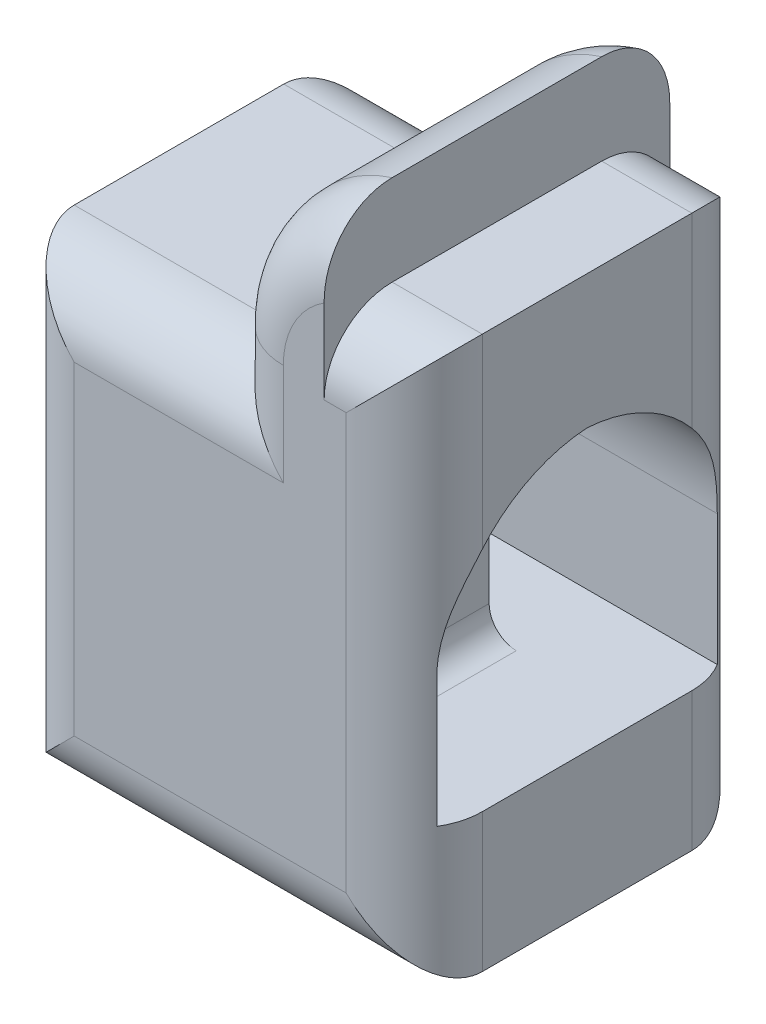
SolidWorks part; units mm, degrees
ref_plane "Front Plane" through (0, 0, 0) normal (0, 0, 1) x (1, 0, 0)
ref_plane "Top Plane" through (0, 0, 0) normal (0, 1, 0) x (1, 0, 0)
ref_plane "Right Plane" through (0, 0, 0) normal (1, 0, 0) x (0, 0, -1)
sketch "Sketch1" plane through (0, 0, 0) normal (0, 0, 1) x (1, 0, 0)
  line L0 (-139.1464, 0) -> (210.8536, 0) construction
  line L2 (-144.0044, -48.147) -> (166.7822, -48.147)
  line L3 (-144.0044, -48.147) -> (-144.0044, 51.853)
  line L4 (-144.0044, 51.853) -> (129.8735, 51.853)
  line L5 (226.7822, 11.853) -> (226.7822, 46.0483)
  line L6 (162.976, 133.7076) -> (166.7822, 133.7076)
  line L7 (129.8735, 103.7076) -> (129.8735, 51.853)
  line L9 (226.7822, 73.7076) -> (226.7822, 46.0483)
  line L12 (129.8735, 103.7076) -> (162.976, 103.7076)
  line L13 (162.976, 133.7076) -> (162.976, 103.7076)
  arc A0 (166.7822, 133.7076) -> (226.7822, 73.7076) centre (166.7822, 73.7076) cw
  arc A1 (166.7822, -48.147) -> (226.7822, 11.853) centre (166.7822, 11.853) ccw
  dimension "D2" = 60
  dimension "D1" = 350
  dimension "D3" = 30
  dimension "D4" = 100
sketch "Sketch2" plane through (0, 0, 0) normal (0, 0, 1) x (1, 0, 0)
  line L1 (-37.0212, -102.3945) -> (112.9173, -102.3945)
  line L2 (-37.0212, -102.3945) -> (-37.0212, 66.5681)
  line L3 (-37.0212, 66.5681) -> (39.8215, 66.5681)
  line L4 (112.9173, -102.3945) -> (112.9173, 63.3181)
  line L5 (129.8735, 103.7076) -> (162.976, 103.7076) construction
  line L7 (112.9173, 63.3181) -> (112.9173, 100.4576)
  line L12 (112.9173, 100.4576) -> (79.8148, 100.4576)
  line L13 (79.8148, 133.7076) -> (79.8148, 100.4576)
  line L14 (39.8215, 78.9736) -> (39.8215, 66.5681)
  arc A0 (39.8215, 78.9736) -> (79.8148, 133.7076) centre (97.272, 78.9736) cw
  dimension "D1" = 33.25
extrude "Boss-Extrude1" add sketch "Sketch2" along normal mid plane 127
sketch "Sketch3" plane through (112.9173, 0, 0) normal (1, 0, 0) x (0, 0, -1)
  line L5 (51.5, 51.5) -> (-51.5, 51.5)
  line L6 (51.5, 51.5) -> (51.5, -51.5)
  line L7 (51.5, -51.5) -> (-51.5, -51.5)
  line L8 (-51.5, 51.5) -> (-51.5, -51.5)
  line L9 (51.5, 51.5) -> (-51.5, -51.5) construction
  line L10 (51.5, -51.5) -> (-51.5, 51.5) construction
  point P0 (0, 0)
  dimension "D1" = 103
  dimension "D2" = 103
extrude "Cut-Extrude1" cut sketch "Sketch3" against normal through all
ref_plane "Plane1" through (37.9481, 0, 0) normal (-1, 0, 0) x (0, 0, 1)
sketch "Sketch5" plane through (37.9481, 0, 0) normal (-1, 0, 0) x (0, 0, 1)
  line L0 (51.5, -51.5) -> (-51.5, -51.5) construction
  line L1 (19, -51.5) -> (-19, -51.5)
  line L2 (19, -51.5) -> (19, -21.5)
  line L4 (-19, -51.5) -> (-19, -21.5)
  line L5 (0, -48.147) -> (0, 11.853) construction
  line L6 (-51.5, 51.5) -> (51.5, 51.5) construction
  arc A0 (19, -21.5) -> (-19, -21.5) centre (0, -21.5) ccw
  point P12 (-24.6088, -51.5)
  dimension "D1" = 38
  dimension "D2" = 73
extrude "Boss-Extrude2" add sketch "Sketch5" along normal mid plane 40
fillet "Fillet1" radius 55 2 edges at (37.9481, 51.5, 51.5) (37.9481, 51.5, -51.5)
sketch "Sketch6" plane through (17.9481, 0, 0) normal (-1, 0, 0) x (0, 0, 1)
  circle A0 centre (0, -21.5) radius 10
  dimension "D1" = 20
extrude "Cut-Extrude2" cut sketch "Sketch6" against normal through all
fillet "Fillet2" radius 10 2 edges at (57.9481, -51.5, 0) (17.9481, -51.5, 0)
sketch "Sketch7" plane through (112.9173, 0, 0) normal (1, 0, 0) x (0, 0, -1)
  line L1 (-12.8471, -33.7257) -> (12.1529, -33.7257)
  line L2 (-12.8471, -33.7257) -> (-12.8471, -8.7257)
  line L3 (-12.8471, -8.7257) -> (12.1529, -8.7257)
  line L4 (12.1529, -33.7257) -> (12.1529, -8.7257)
  line L6 (12.1529, -33.7257) -> (37.1529, -33.7257)
  line L7 (37.1529, -33.7257) -> (37.1529, -8.7257)
  line L8 (12.1529, -33.7257) -> (12.1529, -8.7257)
  line L9 (12.1529, -8.7257) -> (37.1529, -8.7257)
  line L10 (37.1529, -33.7257) -> (62.1529, -33.7257)
  line L11 (62.1529, -33.7257) -> (62.1529, -8.7257)
  line L12 (37.1529, -33.7257) -> (37.1529, -8.7257)
  line L13 (37.1529, -8.7257) -> (62.1529, -8.7257)
  line L14 (62.1529, -33.7257) -> (87.1529, -33.7257)
  line L15 (87.1529, -33.7257) -> (87.1529, -8.7257)
  line L16 (62.1529, -33.7257) -> (62.1529, -8.7257)
  line L17 (62.1529, -8.7257) -> (87.1529, -8.7257)
  line L18 (87.1529, -33.7257) -> (112.1529, -33.7257)
  line L19 (112.1529, -33.7257) -> (112.1529, -8.7257)
  line L20 (87.1529, -33.7257) -> (87.1529, -8.7257)
  line L21 (87.1529, -8.7257) -> (112.1529, -8.7257)
  line L22 (112.1529, -33.7257) -> (137.1529, -33.7257)
  line L23 (137.1529, -33.7257) -> (137.1529, -8.7257)
  line L24 (112.1529, -33.7257) -> (112.1529, -8.7257)
  line L25 (112.1529, -8.7257) -> (137.1529, -8.7257)
  line L26 (12.1529, -8.7257) -> (37.1529, -8.7257)
  line L27 (37.1529, -8.7257) -> (37.1529, 16.2743)
  line L28 (12.1529, -8.7257) -> (12.1529, 16.2743)
  line L29 (12.1529, 16.2743) -> (37.1529, 16.2743)
  line L30 (37.1529, -8.7257) -> (62.1529, -8.7257)
  line L31 (62.1529, -8.7257) -> (62.1529, 16.2743)
  line L32 (37.1529, -8.7257) -> (37.1529, 16.2743)
  line L33 (37.1529, 16.2743) -> (62.1529, 16.2743)
  line L34 (62.1529, -8.7257) -> (87.1529, -8.7257)
  line L35 (87.1529, -8.7257) -> (87.1529, 16.2743)
  line L36 (62.1529, -8.7257) -> (62.1529, 16.2743)
  line L37 (62.1529, 16.2743) -> (87.1529, 16.2743)
  line L38 (87.1529, -8.7257) -> (112.1529, -8.7257)
  line L39 (112.1529, -8.7257) -> (112.1529, 16.2743)
  line L40 (87.1529, -8.7257) -> (87.1529, 16.2743)
  line L41 (87.1529, 16.2743) -> (112.1529, 16.2743)
  line L42 (112.1529, -8.7257) -> (137.1529, -8.7257)
  line L43 (137.1529, -8.7257) -> (137.1529, 16.2743)
  line L44 (112.1529, -8.7257) -> (112.1529, 16.2743)
  line L45 (112.1529, 16.2743) -> (137.1529, 16.2743)
  line L46 (12.1529, 16.2743) -> (37.1529, 16.2743)
  line L47 (37.1529, 16.2743) -> (37.1529, 41.2743)
  line L48 (12.1529, 16.2743) -> (12.1529, 41.2743)
  line L49 (12.1529, 41.2743) -> (37.1529, 41.2743)
  line L50 (37.1529, 16.2743) -> (62.1529, 16.2743)
  line L51 (62.1529, 16.2743) -> (62.1529, 41.2743)
  line L52 (37.1529, 16.2743) -> (37.1529, 41.2743)
  line L53 (37.1529, 41.2743) -> (62.1529, 41.2743)
  line L54 (62.1529, 16.2743) -> (87.1529, 16.2743)
  line L55 (87.1529, 16.2743) -> (87.1529, 41.2743)
  line L56 (62.1529, 16.2743) -> (62.1529, 41.2743)
  line L57 (62.1529, 41.2743) -> (87.1529, 41.2743)
  line L58 (87.1529, 16.2743) -> (112.1529, 16.2743)
  line L59 (112.1529, 16.2743) -> (112.1529, 41.2743)
  line L60 (87.1529, 16.2743) -> (87.1529, 41.2743)
  line L61 (87.1529, 41.2743) -> (112.1529, 41.2743)
  line L62 (112.1529, 16.2743) -> (137.1529, 16.2743)
  line L63 (137.1529, 16.2743) -> (137.1529, 41.2743)
  line L64 (112.1529, 16.2743) -> (112.1529, 41.2743)
  line L65 (112.1529, 41.2743) -> (137.1529, 41.2743)
  line L66 (12.1529, 41.2743) -> (37.1529, 41.2743)
  line L67 (37.1529, 41.2743) -> (37.1529, 66.2743)
  line L68 (12.1529, 41.2743) -> (12.1529, 66.2743)
  line L69 (12.1529, 66.2743) -> (37.1529, 66.2743)
  line L70 (37.1529, 41.2743) -> (62.1529, 41.2743)
  line L71 (62.1529, 41.2743) -> (62.1529, 66.2743)
  line L72 (37.1529, 41.2743) -> (37.1529, 66.2743)
  line L73 (37.1529, 66.2743) -> (62.1529, 66.2743)
  line L74 (62.1529, 41.2743) -> (87.1529, 41.2743)
  line L75 (87.1529, 41.2743) -> (87.1529, 66.2743)
  line L76 (62.1529, 41.2743) -> (62.1529, 66.2743)
  line L77 (62.1529, 66.2743) -> (87.1529, 66.2743)
  line L78 (87.1529, 41.2743) -> (112.1529, 41.2743)
  line L79 (112.1529, 41.2743) -> (112.1529, 66.2743)
  line L80 (87.1529, 41.2743) -> (87.1529, 66.2743)
  line L81 (87.1529, 66.2743) -> (112.1529, 66.2743)
  line L82 (112.1529, 41.2743) -> (137.1529, 41.2743)
  line L83 (137.1529, 41.2743) -> (137.1529, 66.2743)
  line L84 (112.1529, 41.2743) -> (112.1529, 66.2743)
  line L85 (112.1529, 66.2743) -> (137.1529, 66.2743)
  line L86 (12.1529, 66.2743) -> (37.1529, 66.2743)
  line L87 (37.1529, 66.2743) -> (37.1529, 91.2743)
  line L88 (12.1529, 66.2743) -> (12.1529, 91.2743)
  line L89 (12.1529, 91.2743) -> (37.1529, 91.2743)
  line L90 (37.1529, 66.2743) -> (62.1529, 66.2743)
  line L91 (62.1529, 66.2743) -> (62.1529, 91.2743)
  line L92 (37.1529, 66.2743) -> (37.1529, 91.2743)
  line L93 (37.1529, 91.2743) -> (62.1529, 91.2743)
  line L94 (62.1529, 66.2743) -> (87.1529, 66.2743)
  line L95 (87.1529, 66.2743) -> (87.1529, 91.2743)
  line L96 (62.1529, 66.2743) -> (62.1529, 91.2743)
  line L97 (62.1529, 91.2743) -> (87.1529, 91.2743)
  line L98 (87.1529, 66.2743) -> (112.1529, 66.2743)
  line L99 (112.1529, 66.2743) -> (112.1529, 91.2743)
  line L100 (87.1529, 66.2743) -> (87.1529, 91.2743)
  line L101 (87.1529, 91.2743) -> (112.1529, 91.2743)
  line L102 (112.1529, 66.2743) -> (137.1529, 66.2743)
  line L103 (137.1529, 66.2743) -> (137.1529, 91.2743)
  line L104 (112.1529, 66.2743) -> (112.1529, 91.2743)
  line L105 (112.1529, 91.2743) -> (137.1529, 91.2743)
  line L106 (12.1529, 91.2743) -> (37.1529, 91.2743)
  line L107 (37.1529, 91.2743) -> (37.1529, 116.2743)
  line L108 (12.1529, 91.2743) -> (12.1529, 116.2743)
  line L109 (12.1529, 116.2743) -> (37.1529, 116.2743)
  line L110 (37.1529, 91.2743) -> (62.1529, 91.2743)
  line L111 (62.1529, 91.2743) -> (62.1529, 116.2743)
  line L112 (37.1529, 91.2743) -> (37.1529, 116.2743)
  line L113 (37.1529, 116.2743) -> (62.1529, 116.2743)
  line L114 (62.1529, 91.2743) -> (87.1529, 91.2743)
  line L115 (87.1529, 91.2743) -> (87.1529, 116.2743)
  line L116 (62.1529, 91.2743) -> (62.1529, 116.2743)
  line L117 (62.1529, 116.2743) -> (87.1529, 116.2743)
  line L118 (87.1529, 91.2743) -> (112.1529, 91.2743)
  line L119 (112.1529, 91.2743) -> (112.1529, 116.2743)
  line L120 (87.1529, 91.2743) -> (87.1529, 116.2743)
  line L121 (87.1529, 116.2743) -> (112.1529, 116.2743)
  line L122 (112.1529, 91.2743) -> (137.1529, 91.2743)
  line L123 (137.1529, 91.2743) -> (137.1529, 116.2743)
  line L124 (112.1529, 91.2743) -> (112.1529, 116.2743)
  line L125 (112.1529, 116.2743) -> (137.1529, 116.2743)
  line L126 (12.1529, 116.2743) -> (37.1529, 116.2743)
  line L127 (37.1529, 116.2743) -> (37.1529, 141.2743)
  line L128 (12.1529, 116.2743) -> (12.1529, 141.2743)
  line L129 (12.1529, 141.2743) -> (37.1529, 141.2743)
  line L130 (37.1529, 116.2743) -> (62.1529, 116.2743)
  line L131 (62.1529, 116.2743) -> (62.1529, 141.2743)
  line L132 (37.1529, 116.2743) -> (37.1529, 141.2743)
  line L133 (37.1529, 141.2743) -> (62.1529, 141.2743)
  line L134 (62.1529, 116.2743) -> (87.1529, 116.2743)
  line L135 (87.1529, 116.2743) -> (87.1529, 141.2743)
  line L136 (62.1529, 116.2743) -> (62.1529, 141.2743)
  line L137 (62.1529, 141.2743) -> (87.1529, 141.2743)
  line L138 (87.1529, 116.2743) -> (112.1529, 116.2743)
  line L139 (112.1529, 116.2743) -> (112.1529, 141.2743)
  line L140 (87.1529, 116.2743) -> (87.1529, 141.2743)
  line L141 (87.1529, 141.2743) -> (112.1529, 141.2743)
  line L142 (112.1529, 116.2743) -> (137.1529, 116.2743)
  line L143 (137.1529, 116.2743) -> (137.1529, 141.2743)
  line L144 (112.1529, 116.2743) -> (112.1529, 141.2743)
  line L145 (112.1529, 141.2743) -> (137.1529, 141.2743)
  line L146 (-12.8471, -8.7257) -> (12.1529, -8.7257)
  line L147 (12.1529, -8.7257) -> (12.1529, 16.2743)
  line L148 (-12.8471, -8.7257) -> (-12.8471, 16.2743)
  line L149 (-12.8471, 16.2743) -> (12.1529, 16.2743)
  line L150 (-12.8471, 16.2743) -> (12.1529, 16.2743)
  line L151 (12.1529, 16.2743) -> (12.1529, 41.2743)
  line L152 (-12.8471, 16.2743) -> (-12.8471, 41.2743)
  line L153 (-12.8471, 41.2743) -> (12.1529, 41.2743)
  line L154 (-12.8471, 41.2743) -> (12.1529, 41.2743)
  line L155 (12.1529, 41.2743) -> (12.1529, 66.2743)
  line L156 (-12.8471, 41.2743) -> (-12.8471, 66.2743)
  line L157 (-12.8471, 66.2743) -> (12.1529, 66.2743)
  line L158 (-12.8471, 66.2743) -> (12.1529, 66.2743)
  line L159 (12.1529, 66.2743) -> (12.1529, 91.2743)
  line L160 (-12.8471, 66.2743) -> (-12.8471, 91.2743)
  line L161 (-12.8471, 91.2743) -> (12.1529, 91.2743)
  line L162 (-12.8471, 91.2743) -> (12.1529, 91.2743)
  line L163 (12.1529, 91.2743) -> (12.1529, 116.2743)
  line L164 (-12.8471, 91.2743) -> (-12.8471, 116.2743)
  line L165 (-12.8471, 116.2743) -> (12.1529, 116.2743)
  line L166 (-12.8471, 116.2743) -> (12.1529, 116.2743)
  line L167 (12.1529, 116.2743) -> (12.1529, 141.2743)
  line L168 (-12.8471, 116.2743) -> (-12.8471, 141.2743)
  line L169 (-12.8471, 141.2743) -> (12.1529, 141.2743)
  line L170 (-12.8471, -33.7257) -> (12.1529, -33.7257) construction
  dimension "D1" = 25
  dimension "D2" = 25
  dimension "D5" = 25
  dimension "D3" = 6
  dimension "D4" = 7
fillet "Fillet3" radius 25 14 edges at (39.8215, 72.7709, -63.5) (39.8215, 72.7709, 63.5) (50.8851, 112.8678, -63.5) (37.9481, -102.3945, 63.5) (50.8851, 112.8678, 63.5) (1.4002, 66.5681, 63.5) (-37.0212, -17.9132, 63.5) (112.9173, -0.9684, 63.5) (112.9173, -0.9684, -63.5) (37.9481, -102.3945, -63.5) (-37.0212, -17.9132, -63.5) (1.4002, 66.5681, -63.5) (96.366, 100.4576, -63.5) (96.366, 100.4576, 63.5)
equation "\"D2@Sketch3\"=\"D1@Sketch3\""
